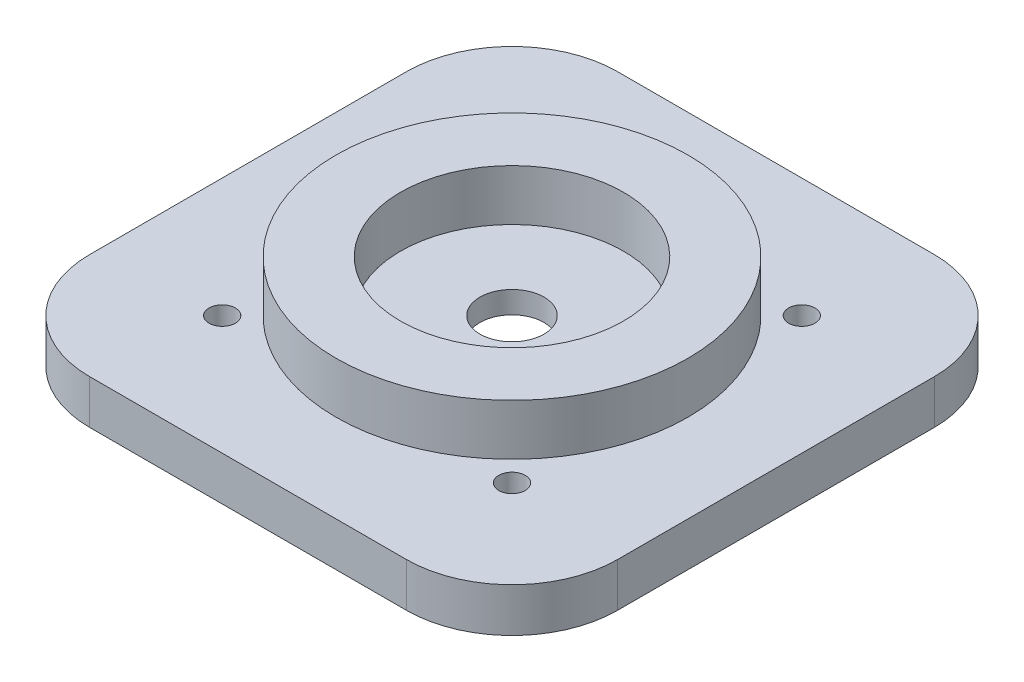
SolidWorks part; units mm, degrees
material "ABS PC"
ref_plane "Front Plane" through (0, 0, 0) normal (0, 0, 1) x (1, 0, 0)
ref_plane "Top Plane" through (0, 0, 0) normal (0, 1, 0) x (1, 0, 0)
ref_plane "Right Plane" through (0, 0, 0) normal (1, 0, 0) x (0, 0, -1)
sketch "Sketch1" plane through (0, 0, 0) normal (0, 1, 0) x (1, 0, 0)
  line L0 (0, 50.8) -> (4.4901, 46.3099)
  line L1 (0, 0) -> (50.8, 0)
  line L2 (0, 0) -> (0, 50.8)
  line L3 (0, 50.8) -> (50.8, 50.8)
  line L4 (50.8, 0) -> (50.8, 50.8)
  line L5 (0, 25.4) -> (50.8, 25.4) construction
  line L6 (25.4, 50.8) -> (25.4, 0) construction
  circle A0 centre (4.4901, 46.3099) radius 1.905
  circle A1 centre (4.4901, 4.4901) radius 1.905
  circle A2 centre (46.3099, 4.4901) radius 1.905
  circle A3 centre (46.3099, 46.3099) radius 1.905
  circle A28 centre (25.4, 25.4) radius 4.625
  dimension "D1" = 3.81
  dimension "D5" = 9.25
  dimension "D2" = 50.8
  dimension "D3" = 50.8
  dimension "D4" = 6.35
extrude "Boss-Extrude1" add sketch "Sketch1" along normal blind 6.35 contours A0 L2 L1 L4 L3 A1 A2 A3 region at (25.4, 0, -50.0816)
sketch "Sketch2" plane through (0, 0, 0) normal (0, 1, 0) x (1, 0, 0)
  line L0 (4.4901, 44.2975) -> (4.4901, 6.5025)
  line L1 (6.5025, 4.4901) -> (44.2975, 4.4901)
  line L2 (46.3099, 44.2975) -> (46.3099, 6.5025)
  line L3 (44.2975, 46.3099) -> (6.5025, 46.3099)
  circle A0 centre (4.4901, 46.3099) radius 1.905
  circle A1 centre (4.4901, 46.3099) radius 2.0124
  circle A2 centre (46.3099, 46.3099) radius 1.905
  circle A3 centre (46.3099, 46.3099) radius 2.0124
  circle A4 centre (46.3099, 4.4901) radius 1.905
  circle A5 centre (46.3099, 4.4901) radius 2.0124
  circle A6 centre (4.4901, 4.4901) radius 1.905
  circle A7 centre (4.4901, 4.4901) radius 2.0124
extrude "Cut-Extrude1" [suppressed] cut sketch "Sketch2" along normal blind 1.5875 from surface contours A7 L1 A5 L2 A3 L3 A1 L0 starting at face at (4.4901, 0, -44.4049)
sketch "Sketch3" plane through (0, 0, 0) normal (0, 1, 0) x (1, 0, 0)
  line L0 (3.2513, 44.2975) -> (3.2513, 6.5025)
  line L1 (6.5025, 3.2513) -> (44.2975, 3.2513)
  line L2 (47.5487, 44.2975) -> (47.5487, 6.5025)
  line L3 (44.2975, 47.5487) -> (6.5025, 47.5487)
  circle A0 centre (3.2513, 47.5487) radius 1.905
  circle A1 centre (3.2513, 47.5487) radius 3.2513
  circle A2 centre (47.5487, 47.5487) radius 1.905
  circle A3 centre (47.5487, 47.5487) radius 3.2513
  circle A4 centre (47.5487, 3.2513) radius 1.905
  circle A5 centre (47.5487, 3.2513) radius 3.2513
  circle A6 centre (3.2513, 3.2513) radius 1.905
  circle A7 centre (3.2513, 3.2513) radius 3.2513
extrude "Cut-Extrude2" [suppressed] cut sketch "Sketch3" against normal blind 1.5875 from surface contours A7 L1 A5 L2 A3 L3 A1 L0 starting at face at (4.4901, 6.35, -44.4049)
fillet "Fillet1" radius 2.54 4 edges at (50.8, 3.175, -50.8) (50.8, 3.175, 0) (0, 3.175, 0) (0, 3.175, -50.8)
sketch "Sketch4" plane through (0, 0, 0) normal (0, -1, 0) x (1, 0, 0)
  line L4 (10.2051, -4.4901) -> (40.5949, -4.4901)
  line L5 (46.3099, -10.2051) -> (46.3099, -40.5949)
  line L6 (40.5949, -46.3099) -> (10.2051, -46.3099)
  line L7 (4.4901, -40.5949) -> (4.4901, -10.2051)
  arc A4 (4.4901, -10.2051) -> (10.2051, -4.4901) centre (4.4901, -4.4901) ccw
  arc A5 (40.5949, -4.4901) -> (46.3099, -10.2051) centre (46.3099, -4.4901) ccw
  arc A6 (46.3099, -40.5949) -> (40.5949, -46.3099) centre (46.3099, -46.3099) ccw
  arc A7 (10.2051, -46.3099) -> (4.4901, -40.5949) centre (4.4901, -46.3099) ccw
  circle A8 centre (4.4901, -4.4901) radius 1.905
  dimension "D1" = 11.43
extrude "Cut-Extrude3" cut sketch "Sketch4" against normal blind 3.175
sketch "Sketch5" plane through (0, 6.35, 0) normal (0, 1, 0) x (1, 0, 0)
  line L8 (63.5, 2.54) -> (63.5, 48.26)
  line L9 (48.26, 63.5) -> (2.54, 63.5)
  line L10 (-12.7, 48.26) -> (-12.7, 2.54)
  line L11 (2.54, -12.7) -> (48.26, -12.7)
  line L12 (63.5, 2.54) -> (63.5, 48.26)
  line L13 (48.26, 63.5) -> (2.54, 63.5)
  line L14 (-12.7, 48.26) -> (-12.7, 2.54)
  line L15 (2.54, -12.7) -> (48.26, -12.7)
  line L16 (50.8, 2.54) -> (50.8, 48.26)
  line L17 (48.26, 50.8) -> (2.54, 50.8)
  line L18 (0, 48.26) -> (0, 2.54)
  line L19 (2.54, 0) -> (48.26, 0)
  line L20 (50.8, 2.54) -> (50.8, 48.26)
  line L21 (48.26, 50.8) -> (2.54, 50.8)
  line L22 (0, 48.26) -> (0, 2.54)
  line L23 (2.54, 0) -> (48.26, 0)
  arc A8 (63.5, 48.26) -> (48.26, 63.5) centre (48.26, 48.26) ccw
  arc A9 (2.54, 63.5) -> (-12.7, 48.26) centre (2.54, 48.26) ccw
  arc A10 (-12.7, 2.54) -> (2.54, -12.7) centre (2.54, 2.54) ccw
  arc A11 (48.26, -12.7) -> (63.5, 2.54) centre (48.26, 2.54) ccw
  arc A12 (63.5, 48.26) -> (48.26, 63.5) centre (48.26, 48.26) ccw
  arc A13 (2.54, 63.5) -> (-12.7, 48.26) centre (2.54, 48.26) ccw
  arc A14 (-12.7, 2.54) -> (2.54, -12.7) centre (2.54, 2.54) ccw
  arc A15 (48.26, -12.7) -> (63.5, 2.54) centre (48.26, 2.54) ccw
  arc A16 (50.8, 48.26) -> (48.26, 50.8) centre (48.26, 48.26) ccw
  arc A17 (2.54, 50.8) -> (0, 48.26) centre (2.54, 48.26) ccw
  arc A18 (0, 2.54) -> (2.54, 0) centre (2.54, 2.54) ccw
  arc A19 (48.26, 0) -> (50.8, 2.54) centre (48.26, 2.54) ccw
  arc A20 (50.8, 48.26) -> (48.26, 50.8) centre (48.26, 48.26) ccw
  arc A21 (2.54, 50.8) -> (0, 48.26) centre (2.54, 48.26) ccw
  arc A22 (0, 2.54) -> (2.54, 0) centre (2.54, 2.54) ccw
  arc A23 (48.26, 0) -> (50.8, 2.54) centre (48.26, 2.54) ccw
  dimension "D1" = 12.7
  dimension "D2" = 0
extrude "Boss-Extrude2" add sketch "Sketch5" against normal up to surface (6.35 mm away) up to face at (25.4, 0, -25.4)
sketch "Sketch6" plane through (0, 6.35, 0) normal (0, 1, 0) x (1, 0, 0)
  circle A0 centre (25.4, 25.4) radius 16.1
  circle A1 centre (25.4, 25.4) radius 25.4
  dimension "D1" = 50.8
  dimension "D2" = 32.2
extrude "Boss-Extrude3" add sketch "Sketch6" along normal blind 7.366
